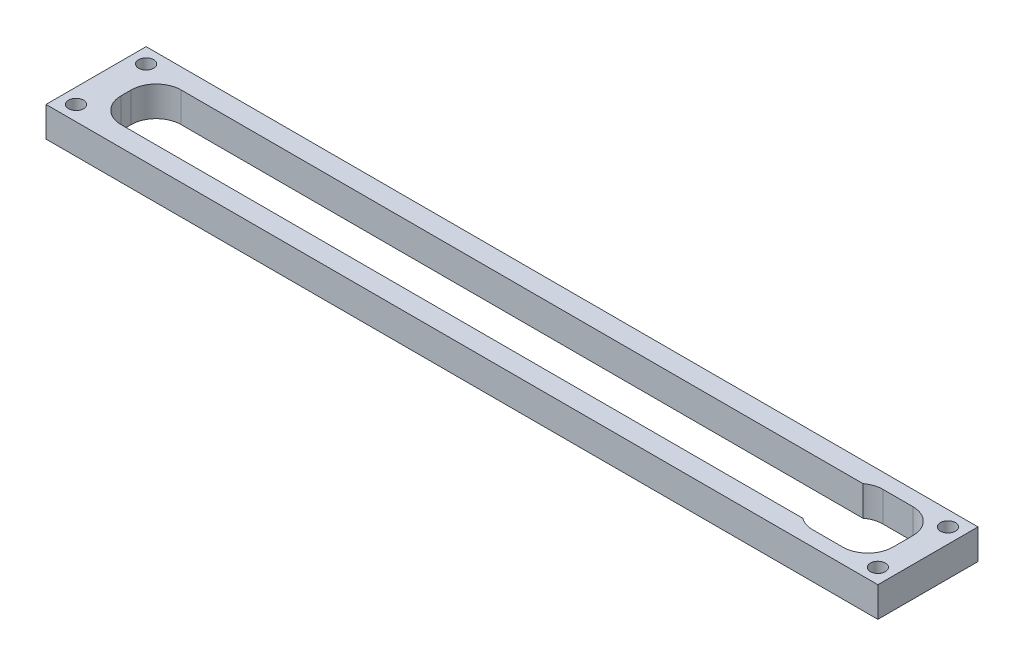
SolidWorks part; units mm, degrees
ref_plane "Front Plane" through (0, 0, 0) normal (0, 0, 1) x (1, 0, 0)
ref_plane "Top Plane" through (0, 0, 0) normal (0, 1, 0) x (1, 0, 0)
ref_plane "Right Plane" through (0, 0, 0) normal (1, 0, 0) x (0, 0, -1)
sketch "Sketch1" plane through (0, 0, 0) normal (0, 1, 0) x (1, 0, 0)
  line L0 (83.0799, 20) -> (83.0799, 0) construction
  line L1 (0, 0) -> (166.1597, 0)
  line L2 (0, 0) -> (0, 20)
  line L3 (0, 20) -> (166.1597, 20)
  line L4 (166.1597, 0) -> (166.1597, 20)
  line L5 (0, 10) -> (166.1597, 10) construction
  line L6 (83.0799, 16) -> (83.0799, 4) construction
  line L7 (6, 16) -> (160.1597, 16)
  line L8 (6, 16) -> (6, 4)
  line L9 (6, 4) -> (160.1597, 4)
  line L10 (160.1597, 16) -> (160.1597, 4)
  line L11 (6, 10) -> (160.1597, 10) construction
  circle A0 centre (3, 17) radius 1.5
  circle A1 centre (3, 3) radius 1.5
  circle A2 centre (163.1597, 3) radius 1.5
  circle A3 centre (163.1597, 17) radius 1.5
  point P17 (83.0799, 10)
  point P18 (83.0799, 10)
  dimension "D7" = 3
  dimension "D1" = 166.1597
  dimension "D2" = 20
  dimension "D3" = 154.1597
  dimension "D4" = 12
  dimension "D5" = 3
  dimension "D6" = 3
extrude "Boss-Extrude1" add sketch "Sketch1" along normal blind 6
sketch "Sketch2" plane through (0, 6, 0) normal (0, 1, 0) x (1, 0, 0)
  line L0 (92, 10) -> (-49908, 10) construction
  line L1 (160.1597, 4) -> (160.1597, 16) construction
  line L2 (147.1597, 17) -> (147.1597, 16)
  line L5 (160.1597, 16) -> (6, 16) construction
  line L6 (154.1597, 17) -> (154.1597, 3) construction
  line L7 (147.1597, 17) -> (161.1597, 17)
  line L9 (147.1597, 3) -> (161.1597, 3)
  line L10 (161.1597, 17) -> (161.1597, 3)
  line L12 (147.1597, 16) -> (160.1597, 16)
  line L13 (160.1597, 16) -> (160.1597, 4)
  line L14 (160.1597, 4) -> (147.1597, 4)
  line L15 (6, 4) -> (160.1597, 4) construction
  line L16 (147.1597, 4) -> (147.1597, 3)
  point P4 (160.1597, 10)
  point P23 (154.1597, 10)
  dimension "D1" = 1
  dimension "D2" = 14
  dimension "D3" = 14
extrude "Cut-Extrude1" cut sketch "Sketch2" against normal through all
fillet "Fillet1" radius 5 6 edges at (161.1597, 3, -17) (161.1597, 3, -3) (147.1597, 3, -17) (147.1597, 3, -3) (6, 3, -4) (6, 3, -16)
equation "\"TrackLength\"= ( ( \"n\" * 28 ) ) / cos ( \"MountAngle\" ) - ( 2 * \"x\" )"
equation "\"D1@Sketch1\"=\"TrackLength\""
equation "\"TrackWidth\"= \"MarbleTrackWidth\" + ( 2 * 4 )"
equation "\"D2@Sketch1\"=\"TrackWidth\""
equation "\"MarbleTrackWidth\"= \"MarbleWidth\" - 1"
equation "\"MarbleTrackLength\"= \"TrackLength\" - ( 2 * 6 )"
equation "\"D3@Sketch1\"=\"MarbleTrackLength\""
equation "\"D4@Sketch1\"=\"MarbleTrackWidth\""
equation "\"MarbleWidth\"= 13"
equation "\"n\"= 6"
equation "\"MountAngle\" = 10"
equation "\"x\"= 14 / cos ( \"MountAngle\" ) - 12"
